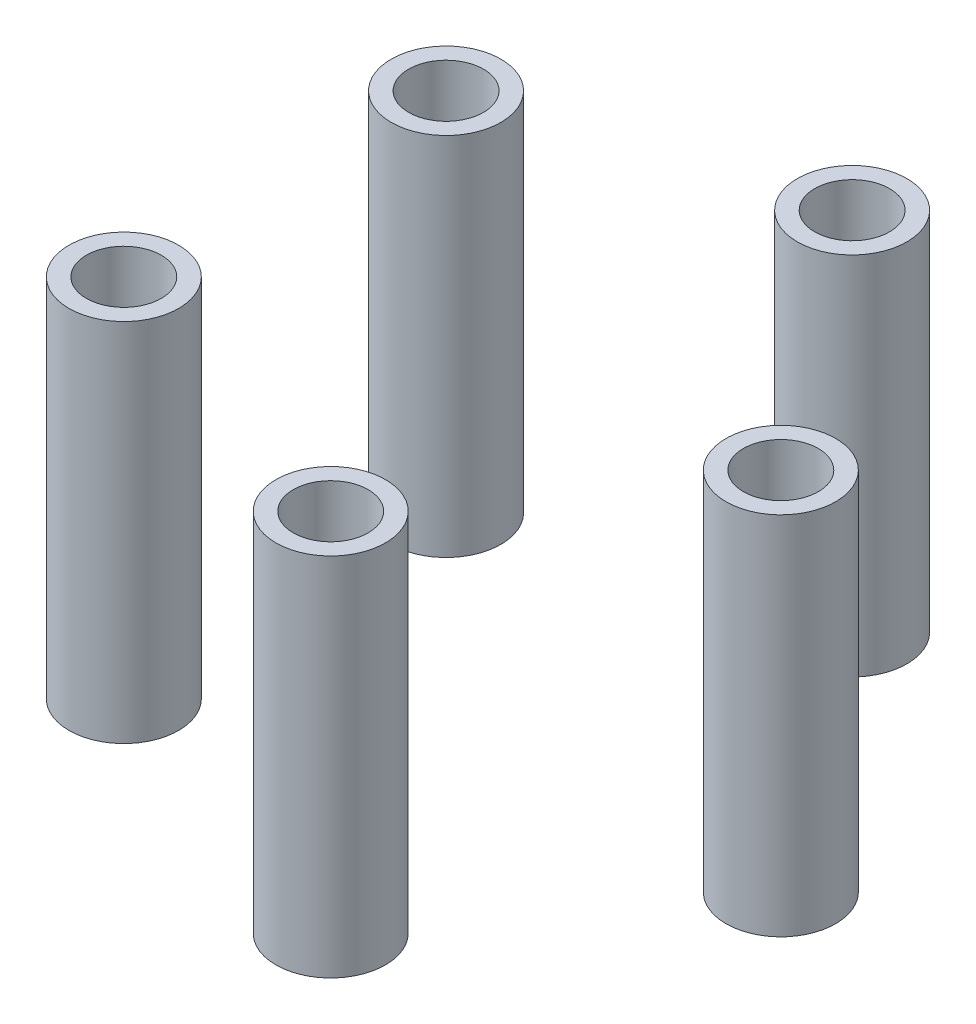
SolidWorks part; units mm, degrees
ref_plane "Front Plane" through (0, 0, 0) normal (0, 0, 1) x (1, 0, 0)
ref_plane "Top Plane" through (0, 0, 0) normal (0, 1, 0) x (1, 0, 0)
ref_plane "Right Plane" through (0, 0, 0) normal (1, 0, 0) x (0, 0, -1)
sketch "Sketch1" plane through (0, 0, 0) normal (0, 1, 0) x (1, 0, 0)
  line L0 (-15.9353, 8.8168) -> (-9.1353, 8.8209) construction
  line L1 (0.8353, 14.2658) -> (7.6353, 14.27) construction
  line L2 (11.2, 0) -> (18, 0.0042) construction
  line L3 (0.8353, -14.2658) -> (7.6353, -14.2617) construction
  line L4 (-15.9353, -8.8168) -> (-9.1353, -8.8126) construction
  circle A0 centre (-12.1353, 8.8168) radius 3.8 construction
  circle A1 centre (-12.9353, 8.8209) radius 3.8 construction
  circle A2 centre (4.6353, 14.2658) radius 3.8 construction
  circle A3 centre (3.8353, 14.27) radius 3.8 construction
  circle A4 centre (15, 0) radius 3.8 construction
  circle A5 centre (14.2, 0.0042) radius 3.8 construction
  circle A6 centre (4.6353, -14.2658) radius 3.8 construction
  circle A7 centre (3.8353, -14.2617) radius 3.8 construction
  circle A8 centre (-12.1353, -8.8168) radius 3.8 construction
  circle A9 centre (-12.9353, -8.8126) radius 3.8 construction
  circle A10 centre (-12.5353, -8.8147) radius 3
  circle A11 centre (4.2353, -14.2638) radius 3
  circle A12 centre (14.6, 0.0021) radius 3
  circle A13 centre (4.2353, 14.2679) radius 3
  circle A14 centre (-12.5353, 8.8189) radius 3
  circle A15 centre (-12.5353, 8.8189) radius 2.05
  circle A16 centre (4.2353, 14.2679) radius 2.05
  circle A17 centre (14.6, 0.0021) radius 2.05
  circle A18 centre (4.2353, -14.2638) radius 2.05
  circle A19 centre (-12.5353, -8.8147) radius 2.05
  dimension "D1" = 4.1
  dimension "D2" = 4.1
  dimension "D3" = 4.1
  dimension "D4" = 4.1
  dimension "D5" = 4.1
extrude "Boss-Extrude1" add sketch "Sketch1" along normal blind 10 and the other way blind 10
